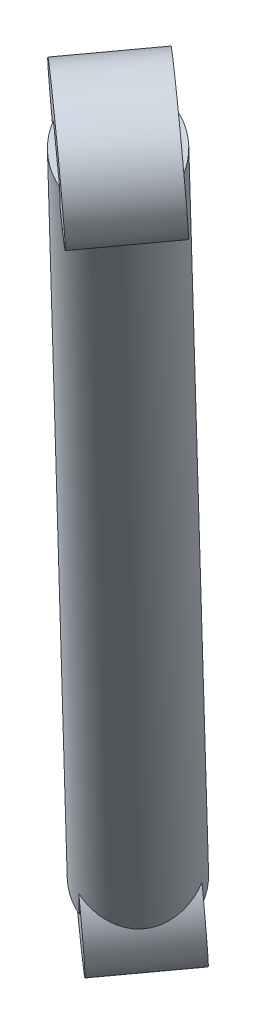
SolidWorks part; units mm, degrees
ref_plane "Plano frontal" through (0, 0, 0) normal (0, 0, 1) x (1, 0, 0)
ref_plane "Plano superior" through (0, 0, 0) normal (0, 1, 0) x (1, 0, 0)
ref_plane "Plano direito" through (0, 0, 0) normal (1, 0, 0) x (0, 0, -1)
sketch3d "SUSP_RR_pushrod_eixo"
  line L0 (503.54, 1408.46, -83.29) -> (338.5589, 1141.1054, -251.4325)
sweep "SUSP_RR_pushrod" add path "SUSP_RR_pushrod_eixo" circular profile diameter 16 parameters "D3"=16
sketch3d "SUSP_RR_pushrod_rod_end_mount_eixo"
  line L0 (508.154, 1408.9115, -88.5347) -> (498.926, 1408.0085, -78.0453)
sweep "SUSP_RR_pushrod_rod_end_mount" add path "SUSP_RR_pushrod_rod_end_mount_eixo" circular profile diameter 22 parameters "D3"=22
sketch3d "SUSP_RR_pushrod_rod_end_rocker_eixo"
  line L0 (343.1729, 1141.5569, -256.6772) -> (333.9449, 1140.6539, -246.1878)
sweep "SUSP_RR_pushrod_rod_end_rocker" add path "SUSP_RR_pushrod_rod_end_rocker_eixo" circular profile diameter 22 parameters "D3"=22
sketch3d "REF_SKETCH"
  line L0 (499.54, 1406.06, -85.09) -> (507.54, 1410.86, -81.49)
  line L1 (505.94, 1405.46, -86.49) -> (501.14, 1411.46, -80.09)
  line L2 (334.5589, 1138.7054, -253.2325) -> (342.5589, 1143.5054, -249.6325)
  line L3 (340.9589, 1138.1054, -254.6325) -> (336.1589, 1144.1054, -248.2325)
ref_point "P_MOUNT"
ref_point "P_ROCKER"
